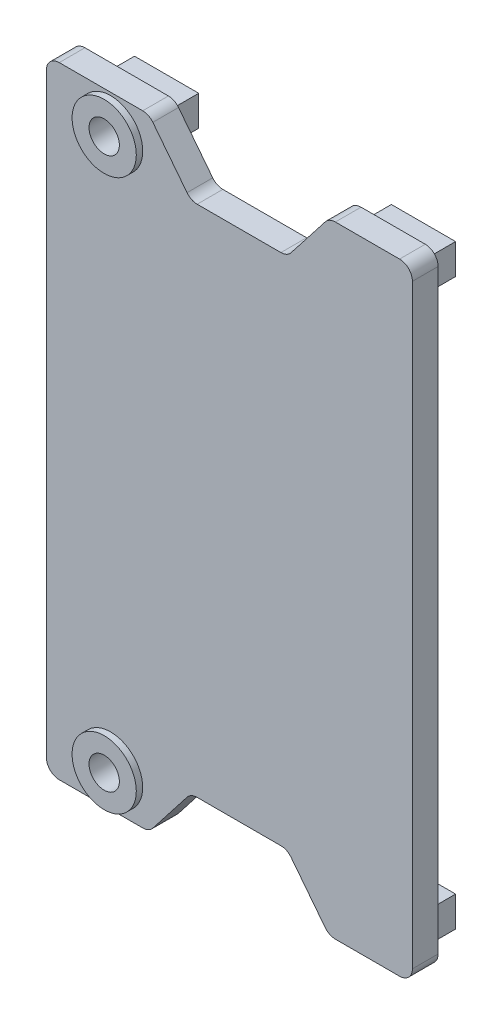
SolidWorks part; units mm, degrees
ref_plane "Front Plane" through (0, 0, 0) normal (0, 0, 1) x (1, 0, 0)
ref_plane "Top Plane" through (0, 0, 0) normal (0, 1, 0) x (1, 0, 0)
ref_plane "Right Plane" through (0, 0, 0) normal (1, 0, 0) x (0, 0, -1)
sketch "Sketch1" plane through (0, 0, 0) normal (0, 0, 1) x (1, 0, 0)
  line L0 (190.5, 25.4) -> (-190.5, -25.4) construction
  line L1 (190.5, -38.1) -> (-190.5, -38.1) construction
  line L2 (190.5, -38.1) -> (190.5, 38.1) construction
  line L3 (190.5, 38.1) -> (-190.5, 38.1) construction
  line L4 (-190.5, -38.1) -> (-190.5, 38.1) construction
  line L5 (190.5, -38.1) -> (-190.5, 38.1) construction
  line L6 (190.5, 38.1) -> (-190.5, -38.1) construction
  line L7 (-190.5, 32.79) -> (190.5, 32.79) construction
  line L8 (-184.15, 30.71) -> (-180.975, 30.71)
  line L9 (190.5, 25.4) -> (-190.5, 25.4) construction
  line L10 (-179.9737, 30.2212) -> (-176.5938, 25.8888)
  line L11 (-166.3062, 25.8888) -> (-162.9263, 30.2212)
  line L12 (-161.925, 30.71) -> (-155.575, 30.71)
  line L13 (-154.305, 29.44) -> (-154.305, 0)
  line L14 (0, 0) -> (-190.5, 0) construction
  line L15 (-154.305, 0) -> (-190.5, 0)
  line L16 (-190.5, 0) -> (-190.5, 25.4)
  line L17 (-175.5925, 25.4) -> (-167.3104, 25.4)
  line L18 (-184.15, 30.71) -> (-189.23, 30.71)
  line L19 (-155.575, 29.44) -> (-161.925, 29.44) construction
  line L20 (-155.575, 29.44) -> (-155.575, 26.44) construction
  line L21 (-155.575, 26.44) -> (-161.925, 26.44) construction
  line L22 (-161.925, 29.44) -> (-161.925, 26.44) construction
  line L23 (-155.575, 29.44) -> (-161.925, 26.44) construction
  line L24 (-155.575, 26.44) -> (-161.925, 29.44) construction
  line L25 (-190.5, 25.4) -> (-190.5, 29.44)
  line L27 (-180.975, 29.44) -> (-187.325, 29.44) construction
  line L28 (-180.975, 29.44) -> (-180.975, 26.44) construction
  line L29 (-180.975, 26.44) -> (-187.325, 26.44) construction
  line L30 (-187.325, 29.44) -> (-187.325, 26.44) construction
  line L31 (-180.975, 29.44) -> (-187.325, 26.44) construction
  line L32 (-180.975, 26.44) -> (-187.325, 29.44) construction
  circle A0 centre (-184.15, 27.2465) radius 5.5436 construction
  circle A1 centre (-184.15, 27.2465) radius 4.5 construction
  circle A2 centre (-184.15, 27.2465) radius 1.5
  circle A3 centre (-184.15, 27.2465) radius 3.175 construction
  arc A4 (-175.5925, 25.4) -> (-176.5938, 25.8888) centre (-175.5925, 26.67) cw
  arc A5 (-167.3104, 25.4) -> (-166.3062, 25.8888) centre (-167.3075, 26.67) ccw
  arc A6 (-162.9263, 30.2212) -> (-161.925, 30.71) centre (-161.925, 29.44) cw
  arc A7 (-154.305, 29.44) -> (-155.575, 30.71) centre (-155.575, 29.44) ccw
  arc A8 (-179.9737, 30.2212) -> (-180.975, 30.71) centre (-180.975, 29.44) ccw
  arc A9 (-189.23, 30.71) -> (-190.5, 29.44) centre (-189.23, 29.44) ccw
  point P0 (0, 0)
  point P27 (-158.75, 27.94)
  point P34 (0, 0)
  point P37 (-176.2125, 25.4)
  point P40 (-166.6875, 25.4)
  point P46 (-176.2125, 25.4)
  point P51 (-190.5, 30.71)
  point P52 (0, 0)
  point P53 (0, 0)
  point P54 (-184.15, 27.94)
  point P59 (-167.3075, 25.4)
  point P60 (0, 0)
  dimension "D3" = 9
  dimension "D4" = 11.0871
  dimension "D6" = 3
  dimension "D7" = 6.35
  dimension "D14" = 1.27
  dimension "D1" = 76.2
  dimension "D2" = 5.31
  dimension "D5" = 6.35
  dimension "D8" = 9.525
  dimension "D9" = 14.2875
  dimension "D10" = 3
  dimension "D11" = 6.35
  dimension "D12" = 27.94
  dimension "D13" = 31.75
  dimension "D15" = 6.35
  dimension "D16" = 6.35
  dimension "D17" = 3
extrude "Boss-Extrude1" add sketch "Sketch1" along normal blind 2.54
sketch "Sketch2" plane through (0, 0, 2.54) normal (0, 0, 1) x (1, 0, 0)
  circle A0 centre (-184.15, 27.2465) radius 1.5
  circle A1 centre (-184.15, 27.2465) radius 3.175
  circle A2 centre (-184.15, 27.2465) radius 1.5 construction
  dimension "D1" = 6.35
extrude "Boss-Extrude2" add sketch "Sketch2" along normal offset from surface (0.635 mm away) 3.175 up to face at (-171.8584, 24.6618, 0)
sketch "Sketch3" plane through (0, 0, 0) normal (0, 0, -1) x (-1, 0, 0)
  line L0 (0, 0) -> (197.0263, 0) construction
  line L1 (187.325, 26.44) -> (180.975, 26.44)
  line L2 (187.325, 26.44) -> (187.325, 29.44)
  line L3 (187.325, 29.44) -> (180.975, 29.44)
  line L4 (180.975, 26.44) -> (180.975, 29.44)
  line L5 (187.325, 26.44) -> (180.975, 29.44) construction
  line L6 (187.325, 29.44) -> (180.975, 26.44) construction
  line L7 (161.925, 26.44) -> (155.575, 26.44)
  line L8 (161.925, 26.44) -> (161.925, 29.44)
  line L9 (161.925, 29.44) -> (155.575, 29.44)
  line L10 (155.575, 26.44) -> (155.575, 29.44)
  line L11 (161.925, 26.44) -> (155.575, 29.44) construction
  line L12 (161.925, 29.44) -> (155.575, 26.44) construction
  line L13 (-190.5, 25.4) -> (190.5, -25.4) construction
  point P0 (184.15, 27.94)
  point P5 (158.75, 27.94)
  point P10 (0, 0)
  dimension "D1" = 6.35
  dimension "D2" = 3
  dimension "D3" = 27.94
  dimension "D4" = 25.4
  dimension "D5" = 6.35
extrude "Boss-Extrude3" add sketch "Sketch3" along normal blind 3
mirror "Mirror1" about plane through (0, 0, 0) normal (0, 1, 0) of bodies 104 102
